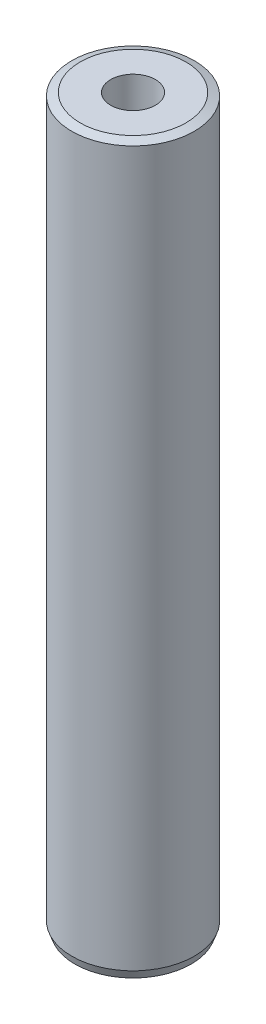
SolidWorks part; units mm, degrees
ref_plane "Front Plane" through (0, 0, 0) normal (0, 0, 1) x (1, 0, 0)
ref_plane "Top Plane" through (0, 0, 0) normal (0, 1, 0) x (1, 0, 0)
ref_plane "Right Plane" through (0, 0, 0) normal (1, 0, 0) x (0, 0, -1)
sketch "Sketch1" plane through (0, 0, 0) normal (0, 1, 0) x (1, 0, 0)
  circle A0 centre (0, 0) radius 40
  dimension "SHAFT_OD" = 80
extrude "Boss-Extrude1" add sketch "Sketch1" along normal blind 473.8834
sketch "Sketch2" plane through (0, 0, 0) normal (0, 1, 0) x (1, 0, 0)
  circle A0 centre (0, 0) radius 14.5887
  dimension "BORE_D" = 29.1774
extrude "Cut-Extrude1" cut sketch "Sketch2" along normal through all
chamfer "Chamfer1" distance 2.015 angle 69.84 2 edges at (0, 473.8834, 40) (0, 0, 40) first distance on face at (0, 473.8834, 40) first distance on face at (0, 0, 14.5887)
